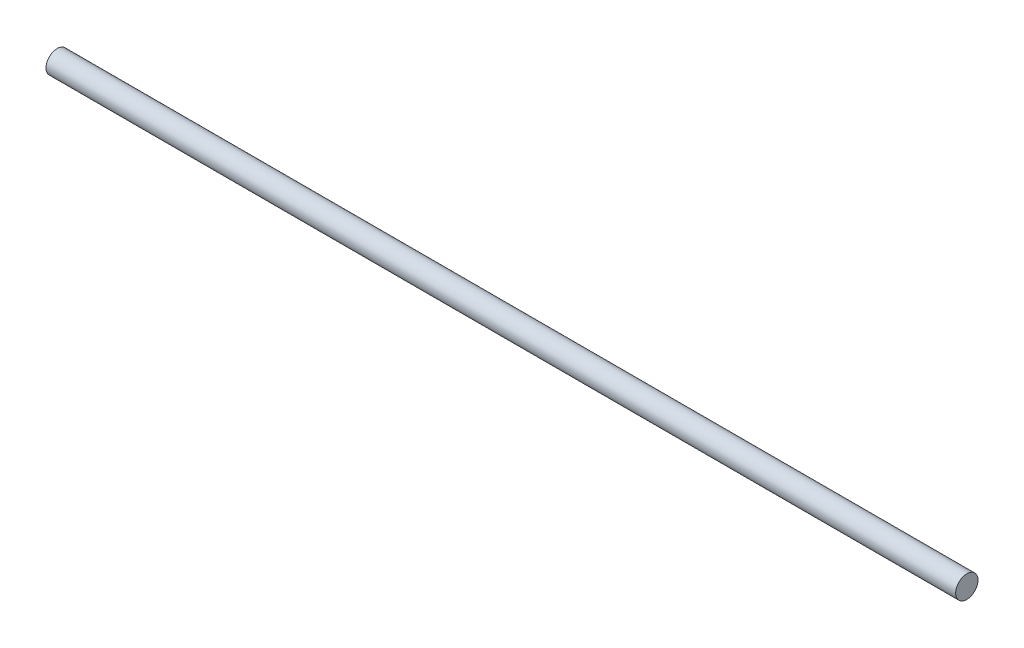
SolidWorks part; units mm, degrees
ref_plane "Front Plane" through (0, 0, 0) normal (0, 0, 1) x (1, 0, 0)
ref_plane "Top Plane" through (0, 0, 0) normal (0, 1, 0) x (1, 0, 0)
ref_plane "Right Plane" through (0, 0, 0) normal (1, 0, 0) x (0, 0, -1)
sketch "Sketch1" plane through (0, 0, 0) normal (1, 0, 0) x (0, 0, -1)
  circle A0 centre (0, 0) radius 3.429
  dimension "D1" = 6.858
extrude "Boss-Extrude1" add sketch "Sketch1" along normal blind 279.4
